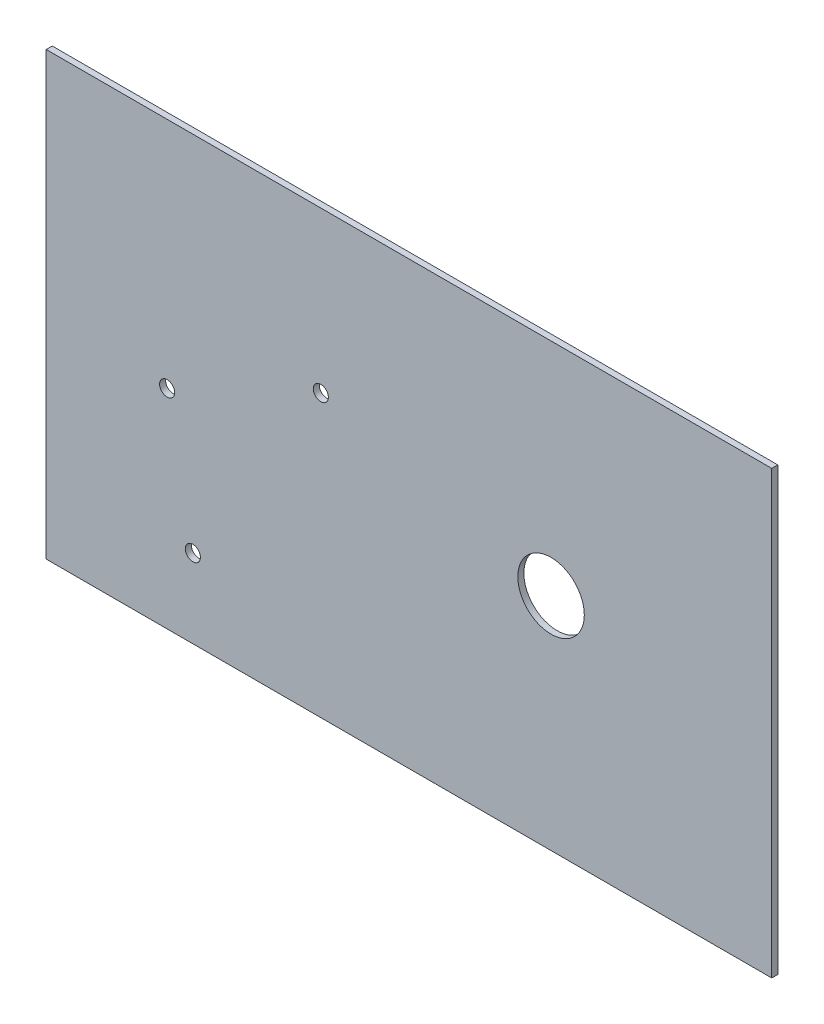
SolidWorks part; units mm, degrees
material "Сталь ШХ15 ГОСТ 801-78"
ref_plane "Plane1" through (0, 0, 0) normal (0, 0, 1) x (1, 0, 0)
ref_plane "Plane2" through (0, 0, 0) normal (0, 1, 0) x (1, 0, 0)
ref_plane "Plane3" through (0, 0, 0) normal (1, 0, 0) x (0, 0, -1)
sketch "Эскиз1" plane through (0, 0, 0) normal (0, 0, 1) x (1, 0, 0)
  line L1 (0, 0) -> (240, 0)
  line L2 (0, 0) -> (0, 146)
  line L3 (0, 146) -> (240, 146)
  line L4 (240, 0) -> (240, 146)
  circle A0 centre (79.7654, 26) radius 11
  circle A1 centre (48.5154, 26) radius 2.5
  circle A2 centre (40, 68.9133) radius 2.5
  circle A3 centre (90.832, 93) radius 2.5
  circle A4 centre (167, 73) radius 11
  point P7 (24.3689, 95.8512)
  point P8 (104.7475, 105.3953)
  point P11 (150.6336, 103.1691)
  point P12 (83.3524, 35.8001)
  point P15 (35.1747, 93.1793)
  point P18 (36.2881, 78.4273)
  dimension "D3" = 22
  dimension "D4" = 53
  dimension "D5" = 5
  dimension "D6" = 31.25
  dimension "D9" = 73
  dimension "D10" = 22
  dimension "D2" = 78.75
  dimension "D7" = 43.75
  dimension "D8" = 56.25
  dimension "D11" = 73
  dimension "D12" = 146
  dimension "D13" = 240
  dimension "D14" = 40
  dimension "D15" = 26
  dimension "D16" = 26
extrude "Бобышка-Вытянуть1" add sketch "Эскиз1" along normal blind 2 contours L2 A0 A1 A2 A3 A4 L4 L3 | L2 L1 L4 A4 A3 A2 A1 A0 | A0 | A0 region at (120.0285, 73.5399, 0) region at (79.7654, 26, 0)
